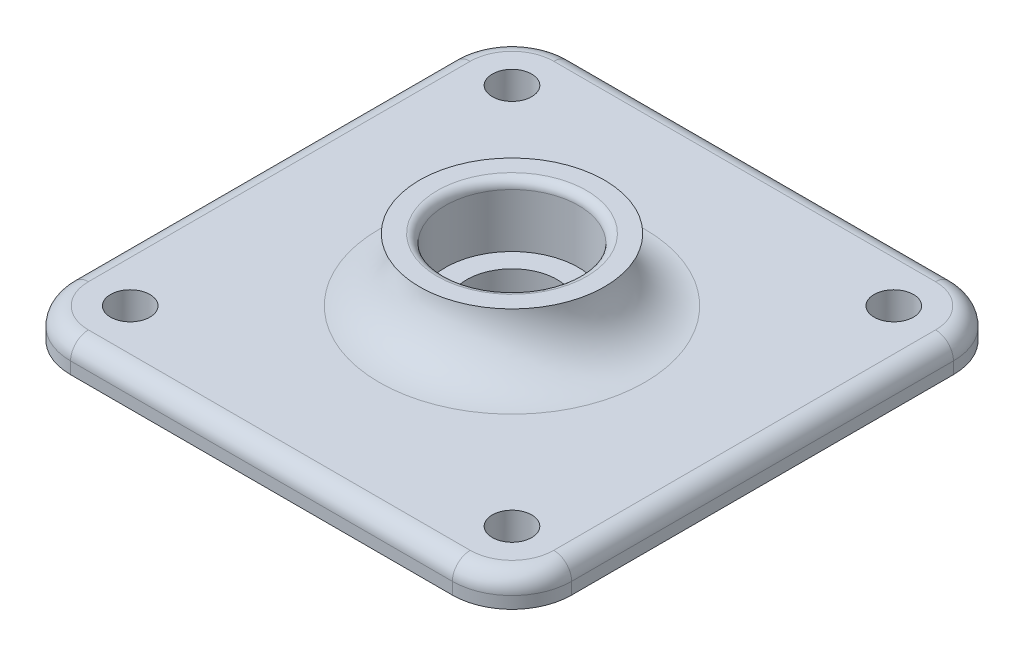
SolidWorks part; units mm, degrees
ref_plane "Front Plane" through (0, 0, 0) normal (0, 0, 1) x (1, 0, 0)
ref_plane "Top Plane" through (0, 0, 0) normal (0, 1, 0) x (1, 0, 0)
ref_plane "Right Plane" through (0, 0, 0) normal (1, 0, 0) x (0, 0, -1)
sketch "Sketch1" plane through (0, 0, 0) normal (0, 1, 0) x (1, 0, 0)
  line L1 (32, 42) -> (-32, 42)
  line L2 (42, 32) -> (42, -32)
  line L3 (32, -42) -> (-32, -42)
  line L4 (-42, 32) -> (-42, -32)
  line L5 (42, 42) -> (-42, -42) construction
  line L6 (42, -42) -> (-42, 42) construction
  arc A0 (32, 42) -> (42, 32) centre (32, 32) cw
  arc A1 (42, -32) -> (32, -42) centre (32, -32) cw
  arc A2 (-32, -42) -> (-42, -32) centre (-32, -32) cw
  arc A3 (-32, 42) -> (-42, 32) centre (-32, 32) ccw
  point P0 (0, 0)
  dimension "D1" = 10
  dimension "D2" = 84
extrude "Boss-Extrude1" add sketch "Sketch1" along normal blind 5 contours L1 A3 L4 A2 L3 A1 L2 A0
sketch "Sketch3" plane through (0, 0, 0) normal (0, 0, 1) x (1, 0, 0)
  line L0 (32, 5) -> (-32, 5) construction
  line L1 (0, 5) -> (-12.5, 5) construction
  line L3 (12.5, 14) -> (-12.5, 14) construction
  line L4 (-12.5, 5) -> (-12.5, 14) construction
  line L5 (-12.5, 5) -> (-11.15, 5)
  line L7 (-12.5, 14) -> (-11.15, 14)
  line L8 (-11.15, 14) -> (-11.15, 5)
  line L9 (-32, 5) -> (-12.5, 5)
  line L10 (0, 0) -> (0, -50000) construction
  line L11 (0, 5) -> (-9.6, 5)
  line L12 (0, 5) -> (0, 0)
  line L13 (-9.6, 5) -> (-9.6, 0)
  line L14 (32, 0) -> (-32, 0) construction
  line L15 (-9.6, 0) -> (0, 0)
  line L16 (-12.5, 15.5) -> (-12.5, 14) construction
  line L17 (-15.5, 11.75) -> (-15.5, 15.5) construction
  line L19 (-15.5, 15.5) -> (-12.5, 15.5)
  arc A0 (-12.5, 14) -> (-22.25, 5) centre (-22.4501, 14.998) cw
  arc A1 (-15.5, 15.5) -> (-12.5, 14) centre (-15.5, 11.75) cw
  arc A2 (-12.5, 15.5) -> (-11.15, 14) centre (-12.6583, 14) cw
  arc A3 (-9.6, 0) -> (-7.6, 5) centre (-7.3717, 2.0087) cw
  dimension "D4" = 10
  dimension "D8" = 3
  dimension "D1" = 12.5
  dimension "D2" = 9
  dimension "D3" = 11.15
  dimension "D5" = 9.6
  dimension "D6" = 1.5
  dimension "D7" = 3
  dimension "D9" = 2
revolve "Revolve2" add sketch "Sketch3" angle 360 about L10 region at (-13.6646, 8.0307, 0) region at (-12.5314, 14.832, 0)
revolve "Cut-Revolve2" cut sketch "Sketch3<5>" angle 360 about L10 region at (-4.7402, 2.4691, 0)
sketch "Sketch3<5>" plane through (0, 0, 0) normal (0, 0, 1) x (1, 0, 0) same geometry as "Sketch3"
fillet "Fillet1" radius 3 8 edges at (42, 5, 0) (39.0711, 5, -39.0711) (0, 5, -42) (-39.0711, 5, -39.0711) (-42, 5, 0) (-39.0711, 5, 39.0711) (0, 5, 42) (39.0711, 5, 39.0711)
sketch "Sketch13" plane through (0, 5, 0) normal (0, 1, 0) x (1, 0, 0)
  line L1 (32, 32) -> (-32, 32) construction
  line L2 (32, 32) -> (32, -32) construction
  line L3 (32, -32) -> (-32, -32) construction
  line L4 (-32, 32) -> (-32, -32) construction
  line L5 (32, 32) -> (-32, -32) construction
  line L6 (32, -32) -> (-32, 32) construction
  point P0 (0, 0)
  dimension "D1" = 64
hole_wizard "M6 Clearance Hole1" positions "Sketch16" profile "Sketch18" hole size "M6" standard "ANSI Metric"
sketch "Sketch16" plane through (0, 5, 0) normal (0, 1, 0) x (1, 0, 0)
  point P0 (-32, 32)
  point P3 (-32, -32)
  point P6 (32, -32)
  point P9 (32, 32)
sketch "Sketch18" plane through (-32, 5, -32) normal (1, 0, 0) x (0, 0, 1)
  line L0 (0, 0) -> (0, 9.9828)
  line L1 (0, 9.9828) -> (3.3, 8)
  line L2 (3.3, 8) -> (3.3, 0)
  line L5 (3.3, 0) -> (0, 0)
  line L10 (0, 9.9828) -> (-3.3, 8) construction
  line L11 (0, -6.35) -> (0, 107.95) construction
  dimension "Hole Dia." = 6.6
  dimension "Hole Depth" = 8
  dimension "Drill Angle" = 118
